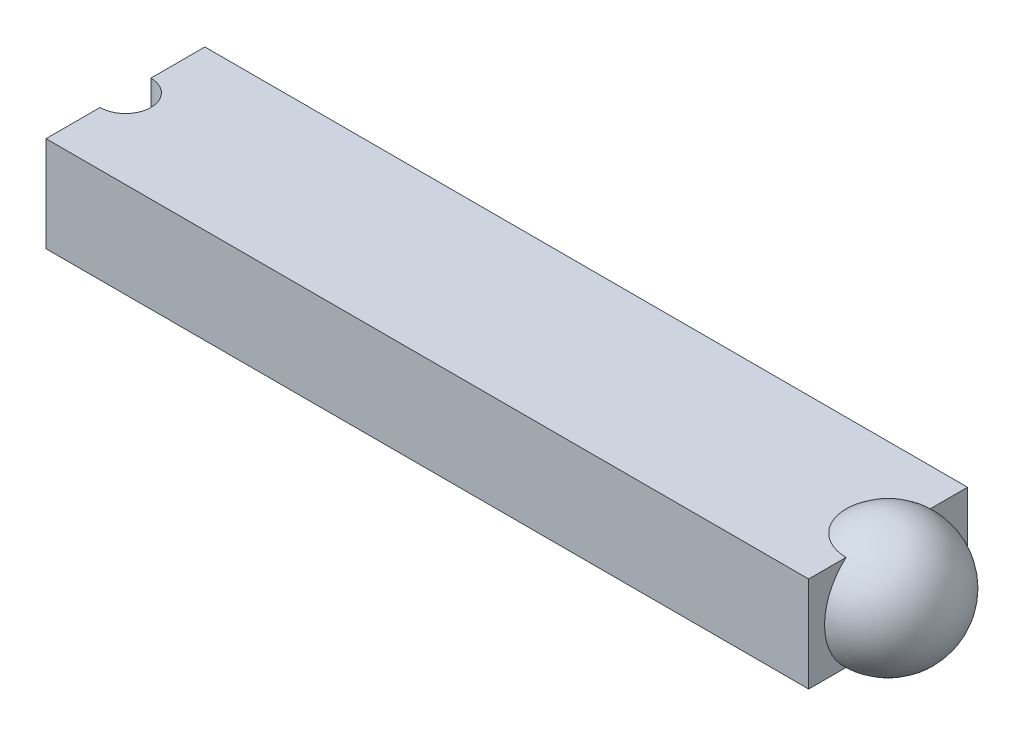
SolidWorks part; units mm, degrees
ref_plane "前视基准面" through (0, 0, 0) normal (0, 0, 1) x (1, 0, 0)
ref_plane "上视基准面" through (0, 0, 0) normal (0, 1, 0) x (1, 0, 0)
ref_plane "右视基准面" through (0, 0, 0) normal (1, 0, 0) x (0, 0, -1)
other "Configuration Table"
sketch "Sketch1" plane through (0, 0, 0) normal (0, 0, 1) x (1, 0, 0)
  line L1 (-12.5, -7.5) -> (12.5, -7.5)
  line L2 (-12.5, -7.5) -> (-12.5, 7.5)
  line L3 (-12.5, 7.5) -> (12.5, 7.5)
  line L4 (12.5, -7.5) -> (12.5, 7.5)
  line L5 (-12.5, -7.5) -> (12.5, 7.5) construction
  line L6 (-12.5, 7.5) -> (12.5, -7.5) construction
  point P0 (0, 0)
sketch "Sketch2" plane through (0, 0, 0) normal (1, 0, 0) x (0, 0, -1)
  line L1 (-12.5, -7.5) -> (12.5, -7.5)
  line L2 (-12.5, -7.5) -> (-12.5, 7.5)
  line L3 (-12.5, 7.5) -> (12.5, 7.5)
  line L4 (12.5, -7.5) -> (12.5, 7.5)
  line L5 (-12.5, -7.5) -> (12.5, 7.5) construction
  line L6 (-12.5, 7.5) -> (12.5, -7.5) construction
  point P0 (0, 0)
extrude "Boss-Extrude1" add sketch "Sketch2" along normal blind 120
ref_plane "Plane1" through (0, -12.5, 0) normal (0, 1, 0) x (1, 0, 0)
sketch "Sketch3" plane through (0, -12.5, 0) normal (0, 1, 0) x (1, 0, 0)
  circle A0 centre (0, 0) radius 4
extrude "Cut-Extrude1" cut sketch "Sketch3" along normal blind 25
sketch "Sketch4" plane through (0, 0, 0) normal (0, 0, 1) x (1, 0, 0)
  line L0 (120, -10) -> (120, 10) construction
  line L1 (120, -10) -> (120, 10)
  arc A0 (120, -10) -> (120, 10) centre (120, 0) ccw
revolve "Revolve1" add sketch "Sketch4" angle 360 about L0
ref_plane "base_side_face" through (0, 12.5, 0) normal (0, 1, 0) x (1, 0, 0)
sketch3d "3DSketch1"
  line L0 (0, -10, 0) -> (0, 10, 0) construction
ref_axis "arm_pitch_axis" through (0, -10, 0) along (0, 1, 0)
sketch3d "3DSketch2"
  line L0 (0, 0, 0) -> (120, 0, 0) construction
ref_axis "arm_longitudinal_axis" through (0, 0, 0) along (1, 0, 0)
